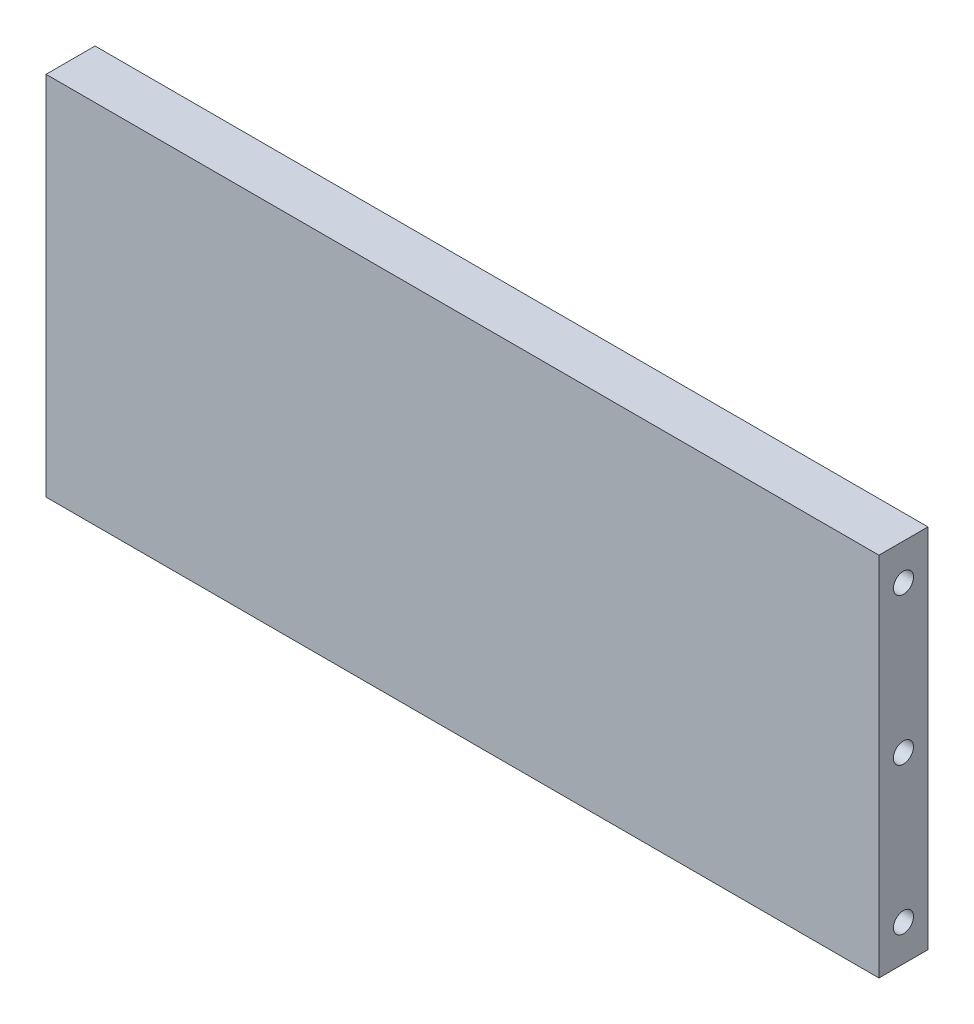
SolidWorks part; units mm, degrees
ref_plane "Front Plane" through (0, 0, 0) normal (0, 0, 1) x (1, 0, 0)
ref_plane "Top Plane" through (0, 0, 0) normal (0, 1, 0) x (1, 0, 0)
ref_plane "Right Plane" through (0, 0, 0) normal (1, 0, 0) x (0, 0, -1)
sketch "Sketch1" plane through (0, 0, 0) normal (1, 0, 0) x (0, 0, -1)
  line L0 (0, 30) -> (0, -30) construction
  line L1 (-5, 37.37) -> (5, 37.37)
  line L2 (-5, 37.37) -> (-5, -37.37)
  line L3 (-5, -37.37) -> (5, -37.37)
  line L4 (5, 37.37) -> (5, -37.37)
  line L5 (-5, 37.37) -> (5, -37.37) construction
  line L6 (-5, -37.37) -> (5, 37.37) construction
  circle A0 centre (0, 30) radius 2.05
  circle A1 centre (0, -30) radius 2.05
  circle A2 centre (0, 0) radius 2.05
  point P0 (0, 0)
  point P8 (0, 0)
  dimension "D3" = 4.1
  dimension "D4" = 4.1
  dimension "D6" = 4.1
  dimension "D1" = 74.74
  dimension "D2" = 60
  dimension "D5" = 10
extrude "Boss-Extrude1" add sketch "Sketch1" along normal mid plane 170
extrude "Boss-Extrude2" add sketch "Sketch1<2>" along normal mid plane 150 contours A0 | A2 | A1 region at (0, 30, 0) region at (0, -30, 0) region at (0, 0, 0)
sketch "Sketch1<2>" plane through (0, 0, 0) normal (1, 0, 0) x (0, 0, -1) same geometry as "Sketch1"
sketch "Sketch2" plane through (0, 0, -5) normal (0, 0, -1) x (-1, 0, 0)
  line L1 (-37, 22) -> (37, 22) construction
  line L2 (-37, 22) -> (-37, -22) construction
  line L3 (-37, -22) -> (37, -22) construction
  line L4 (37, 22) -> (37, -22) construction
  line L5 (-37, 22) -> (37, -22) construction
  line L6 (-37, -22) -> (37, 22) construction
  circle A0 centre (-37, 22) radius 1.75
  circle A1 centre (37, 22) radius 1.75
  circle A2 centre (37, -22) radius 1.75
  circle A3 centre (-37, -22) radius 1.75
  point P0 (0, 0)
  dimension "D3" = 3.5
  dimension "D4" = 3.5
  dimension "D5" = 3.5
  dimension "D6" = 3.5
  dimension "D1" = 74
  dimension "D2" = 44
extrude "Cut-Extrude1" cut sketch "Sketch2" against normal blind 8
sketch "Sketch3" plane through (0, 0, -5) normal (0, 0, -1) x (-1, 0, 0)
  line L1 (-29, 24.5) -> (29, 24.5) construction
  line L2 (-29, 24.5) -> (-29, -24.5) construction
  line L3 (-29, -24.5) -> (29, -24.5) construction
  line L4 (29, 24.5) -> (29, -24.5) construction
  line L5 (-29, 24.5) -> (29, -24.5) construction
  line L6 (-29, -24.5) -> (29, 24.5) construction
  line L7 (-32.5, 28) -> (52.5, 28) construction
  line L8 (-32.5, 28) -> (-32.5, -28) construction
  line L9 (-32.5, -28) -> (52.5, -28) construction
  line L10 (52.5, 28) -> (52.5, -28) construction
  line L11 (-32.5, 28) -> (52.5, -28) construction
  line L12 (-32.5, -28) -> (52.5, 28) construction
  circle A0 centre (-29, 24.5) radius 1.75
  circle A1 centre (29, 24.5) radius 1.75
  circle A2 centre (29, -24.5) radius 1.75
  circle A3 centre (-29, -24.5) radius 1.75
  circle A4 centre (37, -22) radius 1.75 construction
  point P0 (0, 0)
  point P5 (0, 0)
  dimension "D1" = 49
  dimension "D2" = 58
  dimension "D3" = 56
  dimension "D4" = 85
  dimension "D5" = 3.5
extrude "Cut-Extrude2" cut sketch "Sketch3" against normal blind 8
